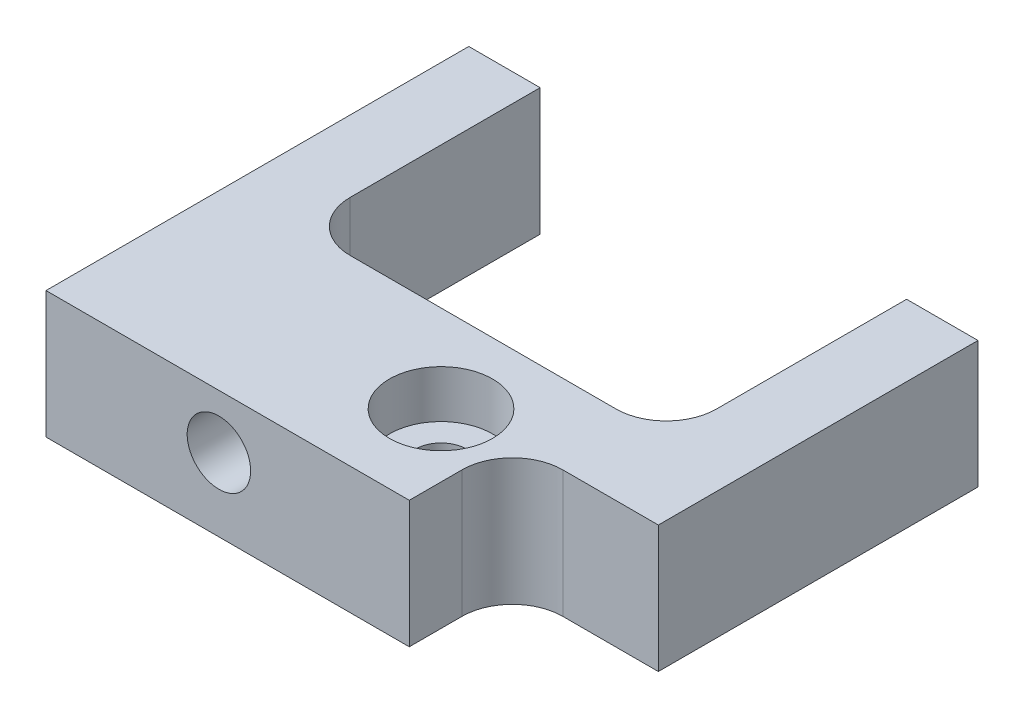
SolidWorks part; units mm, degrees
other "Markup1"
sketch "Sketch8" plane through (21.2, 4, -20.65) normal (0.586, 0.4071, -0.7006) x (0.6806, -0.7165, 0.153)
other "Markup2"
sketch "Sketch9" plane through (-10.9, 4, -20.65) normal (-0.8313, 0.2562, -0.4932) x (0.2592, 0.9637, 0.0638)
material "PTFE (general)"
ref_plane "Front" through (0, 0, 0) normal (0, 0, 1) x (1, 0, 0)
ref_plane "Top" through (0, 0, 0) normal (0, 1, 0) x (1, 0, 0)
ref_plane "Right" through (0, 0, 0) normal (1, 0, 0) x (0, 0, -1)
ref_axis "X" through (-80.9, 0, 0) along (1, 0, 0)
ref_axis "Y" through (0, -50, 0) along (0, 1, 0)
ref_axis "Z" through (0, 0, -80.9) along (0, 0, 1)
sketch "Sketch1" plane through (0, 0, 0) normal (0, 1, 0) x (1, 0, 0)
  line L0 (12, 0.5) -> (12, -6)
  line L1 (12, -6) -> (-10.9, -6)
  line L2 (-10.9, -6) -> (-10.9, 20.65)
  line L3 (-10.9, 20.65) -> (-6.4, 20.65)
  line L4 (16.7, 5.5) -> (-6.4, 5.5)
  line L5 (-6.4, 5.5) -> (-6.4, 20.65)
  line L8 (21.2, 20.65) -> (16.7, 20.65)
  line L10 (16.7, 20.65) -> (16.7, 5.5)
  line L11 (21.2, 20.65) -> (21.2, 0.5)
  line L13 (21.2, 0.5) -> (12, 0.5)
  dimension "D1" = 12
  dimension "D2" = 6
  dimension "D3" = 26.65
  dimension "D4" = 5.5
  dimension "D5" = 10.9
  dimension "D6" = 32.1
  dimension "D7" = 4.5
  dimension "D8" = 5
extrude "Boss-Extrude1" add sketch "Sketch1" along normal mid plane 8
fillet "Fillet1" radius 3.175 3 edges at (12, 0, -0.5) (16.7, 0, -5.5) (-6.4, 0, -5.5)
sketch "Sketch2" plane through (0, 0, 0) normal (0, 0, 1) x (1, 0, 0)
  line L0 (0, 0) -> (0, 0.6) construction
  circle A0 centre (0, 0.6) radius 2
  dimension "D2" = 4
  dimension "D1" = 0.6
extrude "Cut-Extrude1" cut sketch "Sketch2" against normal through all both and the other way through all
sketch "Sketch3" plane through (0, 0, 0) normal (1, 0, 0) x (0, 0, -1)
  line L0 (0, -0.6) -> (0, 0) construction
  circle A0 centre (0, -0.6) radius 2
  dimension "D2" = 4
  dimension "D1" = 0.6
extrude "Cut-Extrude2" cut sketch "Sketch3" against normal through all and the other way blind 4.5
hole_wizard "Ø1.5 (1.5) Diameter Hole1" positions "Sketch4" profile "Sketch5" hole size "Ø1.5" standard "ANSI Metric"
sketch "Sketch4" plane through (0, 0, -20.65) normal (0, 0, -1) x (-1, 0, 0)
  line L0 (-19.05, 0.6) -> (8.75, 0.6) construction
  line L3 (-19.05, 0.6) -> (-21.2, 0.6) construction
  line L4 (-21.2, 4) -> (-21.2, -4) construction
  line L7 (8.75, 0.6) -> (10.9, 0.6) construction
  line L8 (10.9, 4) -> (10.9, -4) construction
  line L10 (6.4, 4) -> (10.9, 4) construction
  point P0 (-19.05, 0.6)
  point P2 (8.75, 0.6)
  dimension "D1" = 3.4
  dimension "D2" = 27.8
sketch "Sketch5" plane through (19.05, 0.6, -20.65) normal (1, 0, 0) x (0, 1, 0)
  line L0 (0, 0) -> (0, 7.4506)
  line L1 (0, 7.4506) -> (0.75, 7)
  line L2 (0.75, 7) -> (0.75, 0)
  line L5 (0.75, 0) -> (0, 0)
  line L10 (0, 7.4506) -> (-0.75, 7) construction
  line L11 (0, -6.35) -> (0, 107.95) construction
  dimension "Hole Dia." = 1.5
  dimension "Hole Depth" = 7
  dimension "Drill Angle" = 118
hole_wizard "CBORE for M3 SHCS1" positions "Sketch6" profile "Sketch7" counterbore size "M3" standard "ANSI Metric" end condition up to next
sketch "Sketch6" plane through (0, 4, 0) normal (0, 1, 0) x (1, 0, 0)
  line L0 (0, 0) -> (8, 0) construction
  point P0 (8, 0)
  dimension "D1" = 8
sketch "Sketch7" plane through (8, 4, 0) normal (1, 0, 0) x (0, 0, 1)
  line L0 (0, 0) -> (0, 8)
  line L1 (0, 8) -> (1.6, 8)
  line L3 (1.6, 8) -> (1.6, 3)
  line L4 (1.6, 3) -> (3.25, 3)
  line L5 (3.25, 3) -> (3.25, 0)
  line L7 (3.25, 0) -> (0, 0)
  line L11 (0, -6.35) -> (0, 107.95) construction
  dimension "Thru Hole Dia." = 3.2
  dimension "Thru Hole Depth" = 8
  dimension "C'Bore Dia." = 6.5
  dimension "C'Bore Depth" = 3
